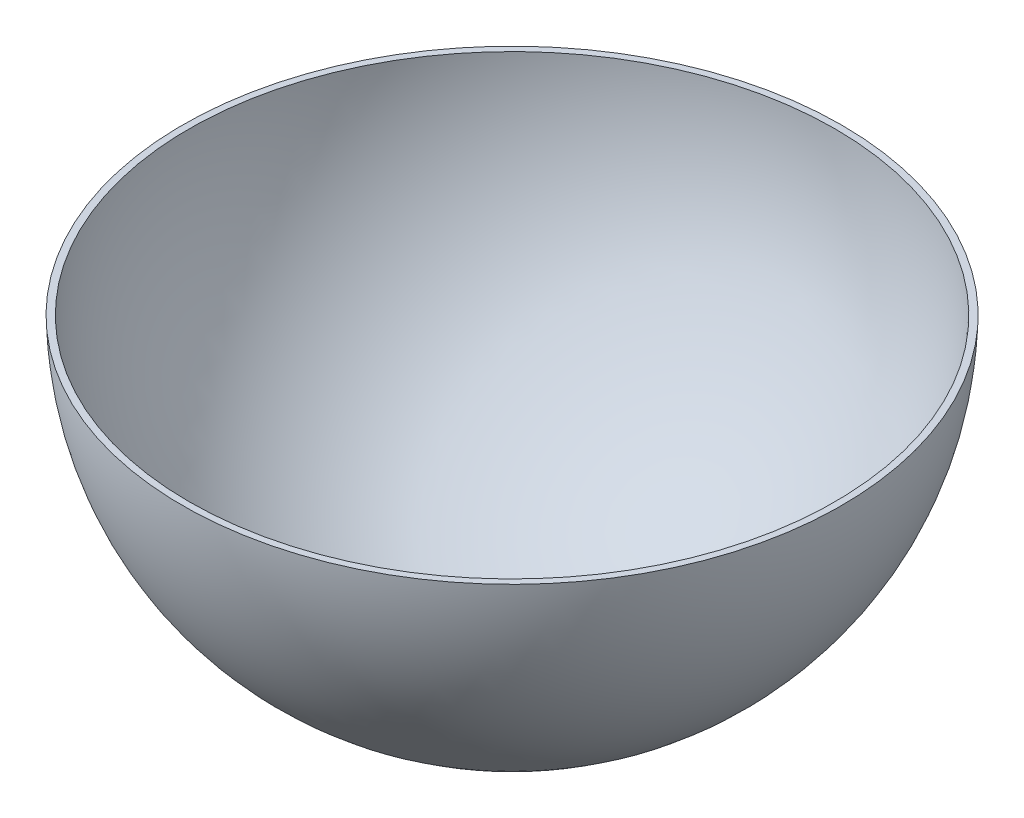
SolidWorks part; units mm, degrees
ref_plane "Front Plane" through (0, 0, 0) normal (0, 0, 1) x (1, 0, 0)
ref_plane "Top Plane" through (0, 0, 0) normal (0, 1, 0) x (1, 0, 0)
ref_plane "Right Plane" through (0, 0, 0) normal (1, 0, 0) x (0, 0, -1)
sketch "Sketch1" plane through (0, 0, 0) normal (1, 0, 0) x (0, 0, -1)
  line L0 (0, 125) -> (0, -125)
  circle A0 centre (0, 0) radius 125
  circle A1 centre (0, 0) radius 122.5
  dimension "D1" = 250
  dimension "D2" = 245
revolve "Revolve1" add sketch "Sketch1" angle 360 about L0 region at (0, 123.75, 2.7951)
sketch "Sketch2" plane through (0, 0, 0) normal (0, 0, 1) x (1, 0, 0)
  line L1 (-160.6226, 162.4244) -> (168.8596, 162.4244)
  line L2 (-160.6226, 162.4244) -> (-160.6226, -3.1938)
  line L3 (-160.6226, -3.1938) -> (168.8596, -3.1938)
  line L4 (168.8596, 162.4244) -> (168.8596, -3.1938)
extrude "Cut-Extrude1" cut sketch "Sketch2" against normal through all both and the other way through all
